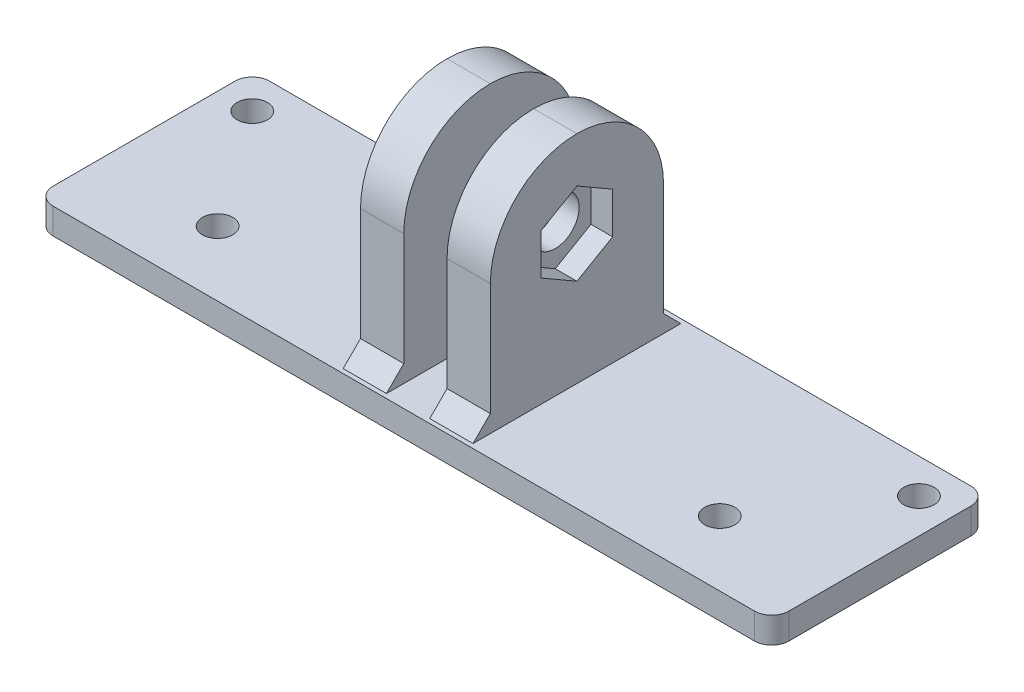
SolidWorks part; units mm, degrees
ref_plane "Front Plane" through (0, 0, 0) normal (0, 0, 1) x (1, 0, 0)
ref_plane "Top Plane" through (0, 0, 0) normal (0, 1, 0) x (1, 0, 0)
ref_plane "Right Plane" through (0, 0, 0) normal (1, 0, 0) x (0, 0, -1)
sketch "Sketch1" plane through (0, 0, 0) normal (0, 1, 0) x (1, 0, 0)
  line L0 (0, 12.5) -> (0, -12.5) construction
  line L1 (-42.5, 12.5) -> (42.5, 12.5)
  line L2 (-42.5, 12.5) -> (-42.5, -12.5)
  line L3 (-42.5, -12.5) -> (42.5, -12.5)
  line L4 (42.5, 12.5) -> (42.5, -12.5)
  dimension "D1" = 25
  dimension "D2" = 85
extrude "Boss-Extrude1" add sketch "Sketch1" along normal blind 3
sketch "Sketch3" plane through (0, 3, 0) normal (0, 1, 0) x (1, 0, 0)
  line L0 (-42.5, 12.5) -> (-42.5, -12.5) construction
  line L1 (42.5, 12.5) -> (-42.5, 12.5) construction
  line L2 (0, -12.5) -> (0, 12.5) construction
  line L3 (-42.5, -12.5) -> (42.5, -12.5) construction
  line L4 (-29, 12.5) -> (-29, -12.5) construction
  circle A0 centre (-38.5, 8.5) radius 1.75
  circle A1 centre (38.5, 8.5) radius 1.75
  circle A2 centre (-29, -5) radius 1.75
  circle A3 centre (29, -5) radius 1.75
  point P14 (0, 0)
  point P15 (-33.4501, -5)
  point P16 (0, 0)
  point P17 (0, 0)
  point P22 (-29, -2.25)
  point P23 (0, 0)
  point P24 (0, 0)
  point P25 (-35.9743, -5)
  dimension "D1" = 3.5
  dimension "D4" = 3.5
  dimension "D2" = 4
  dimension "D3" = 4
  dimension "D5" = 29
  dimension "D6" = 7.5
extrude "Cut-Extrude2" cut sketch "Sketch3" against normal through all
fillet "Fillet2" radius 2 4 edges at (42.5, 1.5, -12.5) (42.5, 1.5, 12.5) (-42.5, 1.5, 12.5) (-42.5, 1.5, -12.5)
sketch "Sketch4" plane through (0, 3, 0) normal (0, 1, 0) x (1, 0, 0)
  line L0 (0, 12.5) -> (0, -12.5) construction
  line L1 (40.5, 12.5) -> (-40.5, 12.5) construction
  line L2 (-40.5, -12.5) -> (40.5, -12.5) construction
  line L3 (-42.5, 0) -> (0, 0) construction
  line L4 (-2.5, 10) -> (-7.5, 10)
  line L5 (-2.5, 10) -> (-2.5, -10)
  line L6 (-2.5, -10) -> (-7.5, -10)
  line L7 (-7.5, 10) -> (-7.5, -10)
  line L8 (-42.5, 10.5) -> (-42.5, -10.5) construction
  line L9 (7.5, 10) -> (7.5, -10)
  line L10 (2.5, -10) -> (7.5, -10)
  line L11 (2.5, 10) -> (2.5, -10)
  line L12 (2.5, 10) -> (7.5, 10)
  point P15 (-2.5, 0)
  dimension "D1" = 5
  dimension "D2" = 2.5
  dimension "D3" = 20
extrude "Boss-Extrude2" add sketch "Sketch4" along normal blind 25
fillet "Fillet3" radius 10 4 edges at (5, 28, 10) (5, 28, -10) (-5, 28, -10) (-5, 28, 10)
sketch "Sketch5" plane through (-7.5, 0, 0) normal (-1, 0, 0) x (0, 0, 1)
  circle A0 centre (0, 18) radius 2.75
  arc A1 (10, 18) -> (0, 28) centre (0, 18) ccw construction
  dimension "D1" = 5.5
extrude "Cut-Extrude3" cut sketch "Sketch5" against normal through all both and the other way through all
sketch "Sketch6" plane through (7.5, 0, 0) normal (1, 0, 0) x (0, 0, -1)
  line L1 (0, 13.2369) -> (4.125, 15.6184)
  line L2 (4.125, 15.6184) -> (4.125, 20.3816)
  line L3 (4.125, 20.3816) -> (0, 22.7631)
  line L4 (0, 22.7631) -> (-4.125, 20.3816)
  line L5 (-4.125, 20.3816) -> (-4.125, 15.6184)
  line L6 (-4.125, 15.6184) -> (0, 13.2369)
  circle A0 centre (0, 18) radius 4.125 construction
  dimension "D1" = 8.25
extrude "Cut-Extrude4" cut sketch "Sketch6" against normal blind 2.5
chamfer "Chamfer1" distance 2 angle 45 4 edges at (5, 3, -10) (-5, 3, -10) (-5, 3, 10) (5, 3, 10)
